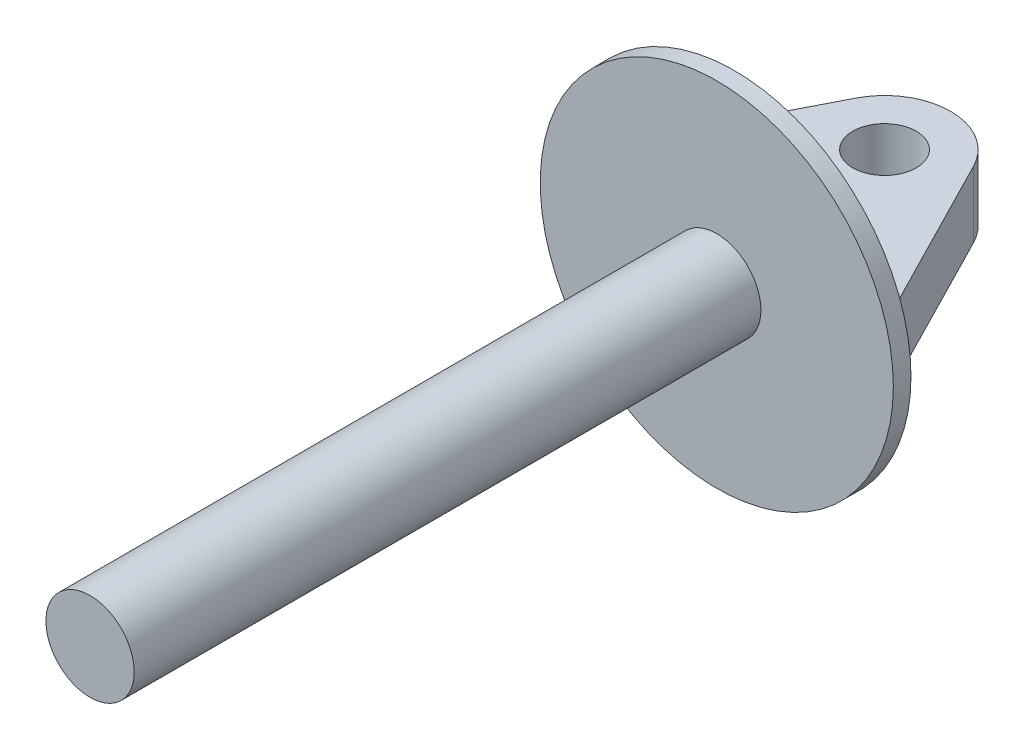
SolidWorks part; units mm, degrees
note: The reader was unsure of these and kept them because the rebuilt part matched: shared geometry of "Sketch1<3>".
material "Plain Carbon Steel"
ref_plane "Front" through (0, 0, 0) normal (0, 0, 1) x (1, 0, 0)
ref_plane "Top" through (0, 0, 0) normal (0, 1, 0) x (1, 0, 0)
ref_plane "Right" through (0, 0, 0) normal (1, 0, 0) x (0, 0, -1)
sketch "Sketch1" plane through (0, 0, 0) normal (0, 0, 1) x (1, 0, 0)
  circle A0 centre (0, 0) radius 12.7
  circle A1 centre (0, 0) radius 11.1125
  circle A2 centre (0, 0) radius 3.175
  dimension "D1" = 25.4
  dimension "D2" = 22.225
  dimension "D3" = 6.35
extrude "Boss-Extrude1" add sketch "Sketch1" along normal blind 2.54 contours A0 A1 | A1 A2 | A2
extrude "Boss-Extrude2" add sketch "Sketch1<3>" along normal blind 47.625 contours A2
sketch "Sketch1<3>" plane through (0, 0, 0) normal (0, 0, 1) x (1, 0, 0) same geometry as "Sketch1"
chamfer "Chamfer1" distance 2.54 distance2 1.27 1 edges at (12.7, 0, 0)
sketch "Sketch2" plane through (0, 0, 0) normal (0, 1, 0) x (1, 0, 0)
  line L0 (-4.2403, 11.6932) -> (-11.1125, -1.7463)
  line L1 (-11.1125, -1.7463) -> (11.1125, -1.7463)
  line L2 (11.1125, -1.7463) -> (4.2403, 11.6932)
  line L3 (-12.7, -2.54) -> (12.7, -2.54) construction
  circle A0 centre (0, 9.525) radius 2.286
  arc A1 (4.2403, 11.6932) -> (-4.2403, 11.6932) centre (0, 9.525) ccw
  point P10 (0, -1.7463)
  dimension "D1" = 4.572
  dimension "D2" = 9.525
  dimension "D3" = 9.525
  dimension "D4" = 0.7937
  dimension "D5" = 22.225
extrude "Boss-Extrude3" add sketch "Sketch2" along normal mid plane 4.7625
fillet "Fillet1" radius 3.175 2 edges
fillet "Fillet2" radius 2.3813 2 edges at (0, -2.3813, 0) (0, 2.3813, 0)
